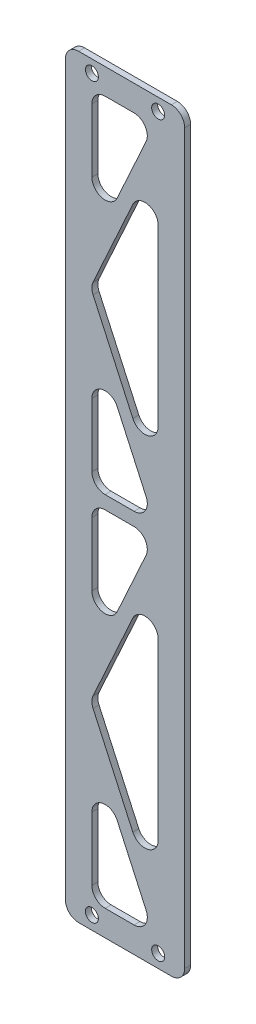
SolidWorks part; units mm, degrees
material "6061-T6 (SS)"
ref_plane "Front Plane" through (0, 0, 0) normal (0, 0, 1) x (1, 0, 0)
ref_plane "Top Plane" through (0, 0, 0) normal (0, 1, 0) x (1, 0, 0)
ref_plane "Right Plane" through (0, 0, 0) normal (1, 0, 0) x (0, 0, -1)
sketch "Sketch1" plane through (0, 0, 0) normal (0, 0, 1) x (1, 0, 0)
  line L0 (-5.08, -5.08) -> (30.48, -5.08)
  line L1 (35.56, 0) -> (35.56, 279.4)
  line L2 (30.48, 284.48) -> (-5.08, 284.48)
  line L3 (-10.16, 279.4) -> (-10.16, 0)
  line L6 (16.1606, 274.32) -> (0, 274.32)
  line L7 (0, 274.32) -> (0, 107.6181)
  line L10 (28.1496, 4.7625) -> (-49966.223, 4.7625) construction
  line L11 (20.7828, 11.9499) -> (9.7022, 36.253)
  line L12 (1052.7568, 4.7625) -> (24.0598, 4.7625) construction
  line L14 (5.08, 4.7625) -> (16.1606, 4.7625)
  line L15 (0.4578, 68.7744) -> (15.6978, 35.3485)
  line L17 (0, 34.1456) -> (0, 9.8425)
  line L18 (0, 70.8819) -> (-50000, 70.8819) construction
  line L19 (0.4578, 72.9893) -> (15.6978, 106.4153)
  line L20 (0, 107.6181) -> (0, 131.9213)
  line L21 (20.7828, 129.8138) -> (9.7022, 105.5107)
  line L22 (5.08, 137.0013) -> (16.1606, 137.0013)
  line L23 (12.7, -5.08) -> (12.7, 49994.92) construction
  line L24 (-10.16, 139.5413) -> (-50010.16, 139.5412) construction
  line L25 (30.48, -5.3975) -> (-5.08, -5.3975)
  line L26 (35.56, 279.0825) -> (35.56, -0.3175)
  line L27 (-5.08, 284.1625) -> (30.48, 284.1625)
  line L28 (-10.16, -0.3175) -> (-10.16, 279.0825)
  line L29 (0.4578, 210.3081) -> (15.6978, 243.734)
  line L30 (0.4578, 206.0932) -> (15.6978, 172.6672)
  line L31 (20.7828, 149.2687) -> (9.7022, 173.5718)
  line L32 (5.08, 142.0813) -> (16.1606, 142.0813)
  line L33 (0, 171.4644) -> (0, 147.1612)
  line L34 (0, 244.9369) -> (0, 269.24)
  line L35 (20.7828, 267.1326) -> (9.7022, 242.8295)
  line L36 (5.08, 274.32) -> (16.1606, 274.32)
  line L37 (25.4, 174.7746) -> (25.4, 241.6266)
  line L38 (25.4, 104.3079) -> (25.4, 37.4559)
  arc A24 (-5.08, 284.48) -> (-10.16, 279.4) centre (-5.08, 279.4) ccw
  arc A25 (35.56, 279.4) -> (30.48, 284.48) centre (30.48, 279.4) ccw
  arc A26 (30.48, -5.08) -> (35.56, 0) centre (30.48, 0) ccw
  arc A27 (-5.08, -5.08) -> (-10.16, 0) centre (-5.08, 0) cw
  arc A28 (0.4578, 72.9893) -> (0.4578, 68.7744) centre (5.08, 70.8819) ccw
  arc A29 (15.6978, 35.3485) -> (25.4, 37.4559) centre (20.32, 37.4559) ccw
  arc A30 (5.08, 4.7625) -> (0, 9.8425) centre (5.08, 9.8425) cw
  arc A31 (9.7022, 36.253) -> (0, 34.1456) centre (5.08, 34.1456) ccw
  arc A32 (20.7828, 11.9499) -> (16.1606, 4.7625) centre (16.1606, 9.8425) cw
  arc A33 (15.6978, 106.4153) -> (25.4, 104.3079) centre (20.32, 104.3079) cw
  arc A34 (9.7022, 105.5107) -> (0, 107.6181) centre (5.08, 107.6181) cw
  arc A35 (5.08, 137.0013) -> (0, 131.9213) centre (5.08, 131.9213) ccw
  arc A36 (20.7828, 129.8138) -> (16.1606, 137.0013) centre (16.1606, 131.9213) ccw
  arc A37 (15.6978, 172.6672) -> (25.4, 174.7746) centre (20.32, 174.7746) ccw
  arc A38 (35.56, -0.3175) -> (30.48, -5.3975) centre (30.48, -0.3175) cw
  arc A39 (30.48, 284.1625) -> (35.56, 279.0825) centre (30.48, 279.0825) cw
  arc A40 (-5.08, -5.3975) -> (-10.16, -0.3175) centre (-5.08, -0.3175) cw
  arc A41 (-5.08, 284.1625) -> (-10.16, 279.0825) centre (-5.08, 279.0825) ccw
  arc A42 (15.6978, 243.734) -> (25.4, 241.6266) centre (20.32, 241.6266) cw
  arc A43 (0.4578, 206.0932) -> (0.4578, 210.3081) centre (5.08, 208.2006) cw
  arc A44 (9.7022, 173.5718) -> (0, 171.4644) centre (5.08, 171.4644) ccw
  arc A45 (20.7828, 149.2687) -> (16.1606, 142.0813) centre (16.1606, 147.1612) cw
  arc A46 (5.08, 142.0813) -> (0, 147.1612) centre (5.08, 147.1612) cw
  arc A47 (9.7022, 242.8295) -> (0, 244.9369) centre (5.08, 244.9369) cw
  arc A48 (5.08, 274.32) -> (0, 269.24) centre (5.08, 269.24) ccw
  arc A49 (20.7828, 267.1326) -> (16.1606, 274.32) centre (16.1606, 269.24) ccw
  circle A50 centre (0, 279.4) radius 2.4892
  circle A51 centre (25.4, 279.4) radius 2.4892
  circle A52 centre (25.4, 0) radius 2.4892
  circle A53 centre (0, 0) radius 2.4892
  point P55 (0, 57.533)
  point P80 (12.7, -5.08)
  dimension "D8" = 5.08
  dimension "D9" = 5.08
  dimension "D1" = 5.08
  dimension "D2" = 5.08
  dimension "D3" = 10.16
  dimension "D4" = 22.86
  dimension "D5" = 5.08
  dimension "D6" = 10.16
  dimension "D7" = 10.16
  dimension "D10" = 134.7788
  dimension "D12" = 11.0806
  dimension "D13" = 2.54
extrude "Boss-Extrude1" add sketch "Sketch1" along normal blind 2.286 contours L27 A41 L3 A27 L0 A26 L1 A39 A49 L35 A47 A43 L29 A42 L37 A37 L30 A44 L31 A45 L32 A46 A35 L22 A36 L21 A34 L7 L6 region at (12.7244, 139.4515, 0)
fillet "Fillet1" radius 5.08 1 edges at (0, 274.32, 1.143)
